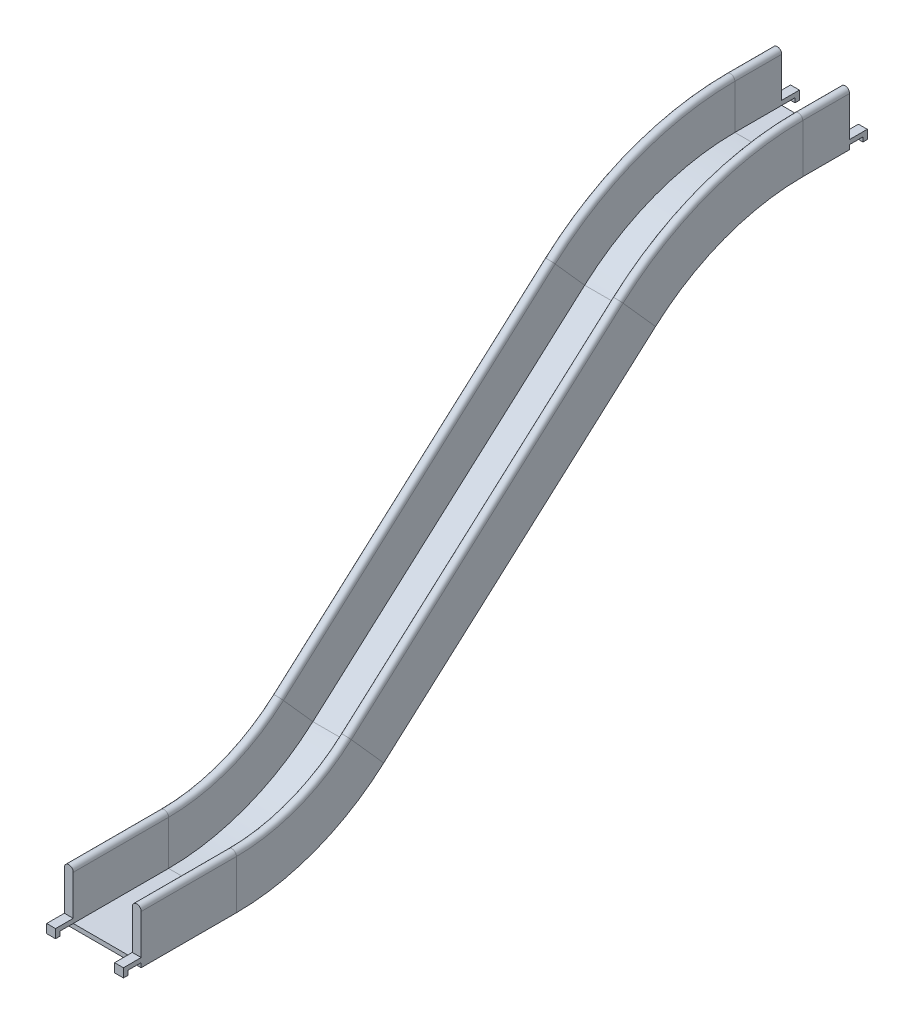
SolidWorks part; units mm, degrees
ref_plane "Front Plane" through (0, 0, 0) normal (0, 0, 1) x (1, 0, 0)
ref_plane "Top Plane" through (0, 0, 0) normal (0, 1, 0) x (1, 0, 0)
ref_plane "Right Plane" through (0, 0, 0) normal (1, 0, 0) x (0, 0, -1)
sketch "Sketch1" plane through (0, 0, 0) normal (0, 0, 1) x (1, 0, 0)
  line L0 (-4.3333, 0) -> (4.3333, 0)
  line L1 (0, 0) -> (0, 4.9358) construction
  line L2 (-4.3333, 0) -> (-3.3333, 0)
  line L3 (-4.3333, 0) -> (-4.3333, 5.5)
  line L5 (-3.3333, 0.5) -> (-3.3333, 5.5)
  line L7 (3.3333, 0.5) -> (3.3333, 5.5)
  line L8 (4.3333, 0) -> (3.3333, 0)
  line L9 (4.3333, 0) -> (4.3333, 5.5)
  line L10 (-3.3333, 0.5) -> (3.3333, 0.5)
  line L11 (-3.8333, 6) -> (-3.8333, 5.5575) construction
  arc A1 (-3.3333, 5.5) -> (-4.3333, 5.5) centre (-3.8333, 5.5) ccw
  arc A2 (3.3333, 5.5) -> (4.3333, 5.5) centre (3.8333, 5.5) cw
  point P3 (0, 0)
  dimension "D1" = 8.6667
  dimension "D2" = 1
  dimension "D3" = 0.5
ref_plane "Plane1" through (0, 0, 0) normal (1, 0, 0) x (0, 1, 0)
sketch "Sketch2" plane through (0, 0, 0) normal (1, 0, 0) x (0, 1, 0)
  line L0 (0, 0) -> (0, 5.2898)
  line L1 (-6.3318, 21.918) -> (-33.6682, 52.608)
  line L2 (-40, 69.2362) -> (-40, 80)
  arc A0 (0, 5.2898) -> (-6.3318, 21.918) centre (-25, 5.2898) ccw
  arc A1 (-33.6682, 52.608) -> (-40, 69.2362) centre (-15, 69.2362) cw
  point P8 (-13.0366, 33.9957)
  point P9 (-40, 58.1961)
  point P11 (-40, 71.7289)
  point P12 (-40, 69.2362)
  dimension "D3" = 25
  dimension "D1" = 40
  dimension "D2" = 80
sweep "Sweep1" add profiles "Sketch1" path "Sketch2"
sketch "Sketch3" plane through (0, 0, 80) normal (0, 0, 1) x (1, 0, 0)
  line L0 (-4.3333, -34.5) -> (-4.3333, -40) construction
  line L1 (-3.3333, -39.5) -> (-4.3333, -39.5)
  line L2 (-3.3333, -39.5) -> (-3.3333, -39)
  line L3 (-3.3333, -39) -> (-4.3333, -39)
  line L4 (-4.3333, -39.5) -> (-4.3333, -39)
  line L6 (4.3333, -40) -> (4.3333, -34.5) construction
  line L7 (3.3333, -39.5) -> (4.3333, -39.5)
  line L8 (3.3333, -39.5) -> (3.3333, -39)
  line L9 (3.3333, -39) -> (4.3333, -39)
  line L10 (4.3333, -39.5) -> (4.3333, -39)
  line L12 (3.3333, -39) -> (4.3333, -39)
  line L13 (3.3333, -39) -> (3.3333, -40)
  line L14 (3.3333, -40) -> (4.3333, -40)
  line L15 (4.3333, -39) -> (4.3333, -40)
  line L16 (-3.3333, -39) -> (-4.3333, -39)
  line L17 (-3.3333, -39) -> (-3.3333, -40)
  line L18 (-3.3333, -40) -> (-4.3333, -40)
  line L19 (-4.3333, -39) -> (-4.3333, -40)
  line M8 (3.3333, -34.5) -> (3.3333, -39.5)
  line M10 (-3.3333, -39.5) -> (-3.3333, -34.5)
  line M12 (-4.3333, -34.5) -> (-4.3333, -40)
  line M13 (-4.3333, -40) -> (4.3333, -40)
  line M14 (4.3333, -40) -> (4.3333, -34.5)
  dimension "D1" = 0.5
  dimension "D2" = 0.5
extrude "Boss-Extrude1" add sketch "Sketch3" along normal blind 2 contours L3 L1 M10 M12 | L9 L7 M8 M14 region at (-3.8333, -39.25, 80) region at (3.8333, -39.25, 80)
extrude "Boss-Extrude2" add sketch "Sketch3<3>" along normal blind 0.5 from offset 1.5 contours L17 L1 M12 M13 | L7 L13 M13 M14 region at (-3.8333, -39.75, 80) region at (3.8333, -39.75, 80)
sketch "Sketch3<3>" plane through (0, 0, 80) normal (0, 0, 1) x (1, 0, 0) same geometry as "Sketch3"
sketch "Sketch5" plane through (0, 0, 0) normal (0, 0, -1) x (-1, 0, 0)
  line L0 (-4.3333, 0) -> (-4.3333, 5.5) construction
  line L1 (-3.3333, 0.5) -> (-4.3333, 0.5)
  line L2 (-3.3333, 0.5) -> (-3.3333, 1)
  line L3 (-3.3333, 1) -> (-4.3333, 1)
  line L4 (-4.3333, 0.5) -> (-4.3333, 1)
  line L5 (4.3333, 5.5) -> (4.3333, 0) construction
  line L6 (3.3333, 0.5) -> (4.3333, 0.5)
  line L7 (3.3333, 0.5) -> (3.3333, 1)
  line L8 (3.3333, 1) -> (4.3333, 1)
  line L9 (4.3333, 0.5) -> (4.3333, 1)
  line L11 (3.3333, 1) -> (4.3333, 1)
  line L12 (3.3333, 1) -> (3.3333, 0)
  line L13 (3.3333, 0) -> (4.3333, 0)
  line L14 (4.3333, 1) -> (4.3333, 0)
  line L15 (-3.3333, 1) -> (-4.3333, 1)
  line L16 (-3.3333, 1) -> (-3.3333, 0)
  line L17 (-3.3333, 0) -> (-4.3333, 0)
  line L18 (-4.3333, 1) -> (-4.3333, 0)
  line M10 (-4.3333, 5.5) -> (-4.3333, 0)
  line M11 (-4.3333, 0) -> (4.3333, 0)
  line M12 (4.3333, 0) -> (4.3333, 5.5)
  line M14 (3.3333, 5.5) -> (3.3333, 0.5)
  line M16 (-3.3333, 0.5) -> (-3.3333, 5.5)
  dimension "D1" = 0.5
  dimension "D2" = 0.5
extrude "Boss-Extrude3" add sketch "Sketch5" along normal blind 2 contours L8 L6 M14 M12 | L3 L1 M16 M10 region at (3.8333, 0.75, 0) region at (-3.8333, 0.75, 0)
extrude "Boss-Extrude4" add sketch "Sketch5<3>" along normal blind 0.5 from offset 1.5 contours L16 L1 M10 M11 | L6 L12 M11 M12 region at (3.8333, 0.25, 0) region at (-3.8333, 0.25, 0)
sketch "Sketch5<3>" plane through (0, 0, 0) normal (0, 0, -1) x (-1, 0, 0) same geometry as "Sketch5"
